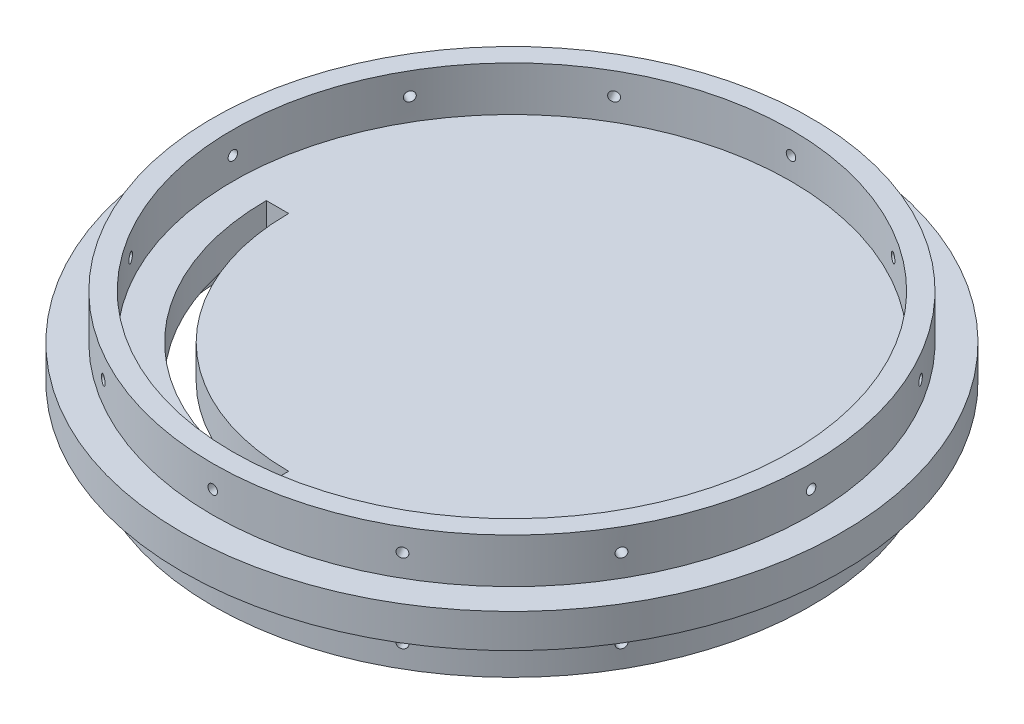
SolidWorks part; units mm, degrees
material "6061-T6 (SS)"
ref_plane "Front Plane" through (0, 0, 0) normal (0, 0, 1) x (1, 0, 0)
ref_plane "Top Plane" through (0, 0, 0) normal (0, 1, 0) x (1, 0, 0)
ref_plane "Right Plane" through (0, 0, 0) normal (1, 0, 0) x (0, 0, -1)
sketch "Sketch1" plane through (0, 0, 0) normal (0, 1, 0) x (1, 0, 0)
  circle A0 centre (0, 0) radius 93.726
  dimension "D1" = 187.452
extrude "Boss-Extrude1" add sketch "Sketch1" along normal mid plane 9.652
sketch "Sketch2" plane through (0, 0, 0) normal (0, 0, 1) x (1, 0, 0)
  line L0 (0, -18.3275) -> (0, 20.8308) construction
  line L1 (0, -4.826) -> (-19.297, -4.826)
  line L2 (-93.726, -4.826) -> (93.726, -4.826) construction
  line L3 (0, -4.826) -> (0, -1.4952)
  line L4 (-0.3818, -1.4952) -> (0, -1.4952)
  arc A0 (-19.297, -4.826) -> (-0.3818, -1.4952) centre (-0.4072, -56.7254) cw
  dimension "D6" = 55.2302
  dimension "D1" = 19.297
  dimension "D2" = 3.3308
  dimension "D3" = 0.3818
revolve "Cut-Revolve1" cut sketch "Sketch2" angle 360 about L0
sketch "Sketch4" plane through (0, 4.826, 0) normal (0, 1, 0) x (1, 0, 0)
  circle A0 centre (0, 0) radius 85.09
  circle A1 centre (0, 0) radius 79.375
  dimension "D1" = 170.18
  dimension "D2" = 158.75
extrude "Boss-Extrude2" add sketch "Sketch4" along normal blind 12.7
ref_plane "Plane1" through (0, 0, -85.09) normal (0, 0, -1) x (-1, 0, 0)
sketch "Sketch5" plane through (0, 0, -85.09) normal (0, 0, -1) x (-1, 0, 0)
  line L0 (0, 19.2786) -> (0, -19.2786) construction
  line L1 (79.375, 17.526) -> (-79.375, 17.526) construction
  circle A0 centre (0, 11.176) radius 1.3525
  dimension "D1" = 2.7051
  dimension "D2" = 6.35
extrude "Cut-Extrude2" cut sketch "Sketch5" against normal blind 12.7
pattern_circular "CirPattern1" count 12 over 360 about axis through (0, 17.526, 0) along (0, -1, 0) of "Cut-Extrude2" reverse direction yes
mirror "Mirror2" about plane through (0, 0, 0) normal (0, 1, 0) of "CirPattern1", "Cut-Extrude2", "Boss-Extrude2"
sketch "Sketch6" plane through (0, 4.826, 0) normal (0, 1, 0) x (1, 0, 0)
  line L0 (-63.5, 0) -> (-69.85, 0)
  line L1 (0, -69.85) -> (0, -63.5)
  line L2 (0, -19.2786) -> (0, 19.2786) construction
  arc A0 (-69.85, 0) -> (0, -69.85) centre (0, 0) ccw
  arc A1 (-63.5, 0) -> (0, -63.5) centre (0, 0) ccw
  dimension "D1" = 69.85
  dimension "D2" = 63.5
  dimension "D3" = 90
extrude "Cut-Extrude3" cut sketch "Sketch6" against normal up to surface (9.652 mm away) up to face at (0, -4.826, -19.297)
